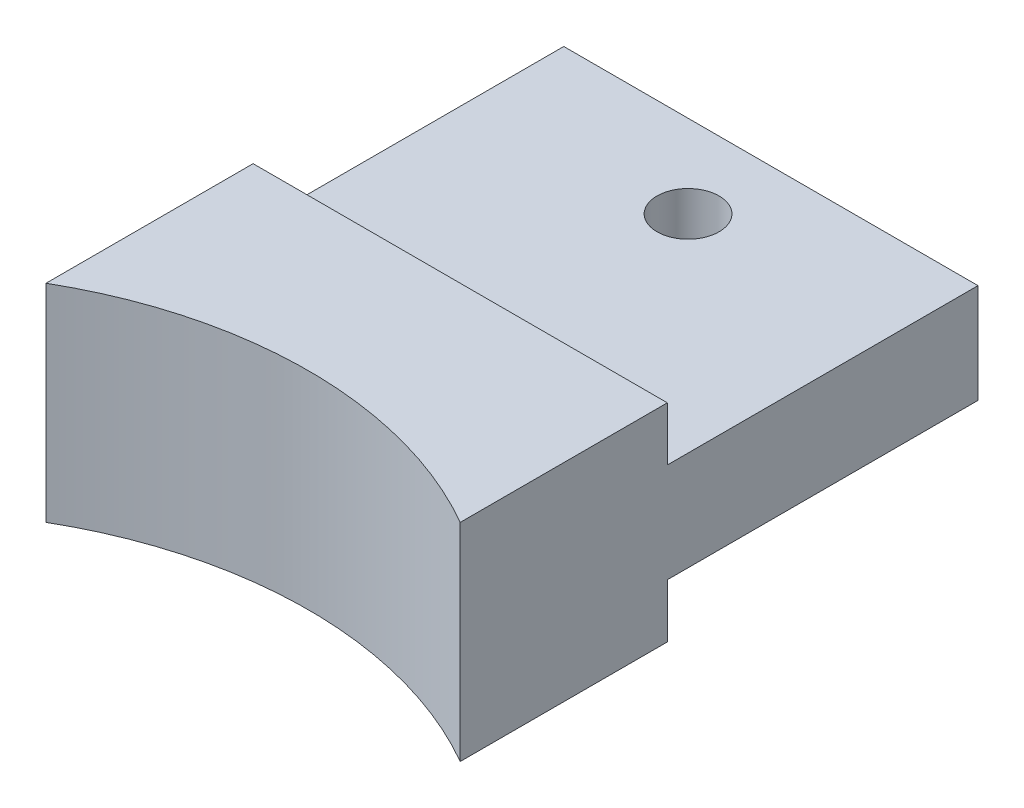
SolidWorks part; units mm, degrees
ref_plane "Front Plane" through (0, 0, 0) normal (0, 0, 1) x (1, 0, 0)
ref_plane "Top Plane" through (0, 0, 0) normal (0, 1, 0) x (1, 0, 0)
ref_plane "Right Plane" through (0, 0, 0) normal (1, 0, 0) x (0, 0, -1)
sketch "Sketch1" plane through (0, 0, 0) normal (0, 0, 1) x (1, 0, 0)
  line L1 (-10, -5) -> (10, -5)
  line L2 (-10, -5) -> (-10, 5)
  line L3 (-10, 5) -> (10, 5)
  line L4 (10, -5) -> (10, 5)
  line L5 (-10, -5) -> (10, 5) construction
  line L6 (-10, 5) -> (10, -5) construction
  point P0 (0, 0)
  dimension "D1" = 10
  dimension "D2" = 20
extrude "Boss-Extrude1" add sketch "Sketch1" along normal blind 10
sketch "Sketch2" plane through (0, 5, 0) normal (0, 1, 0) x (1, 0, 0)
  line L0 (-10, -10) -> (10, -10)
  arc A0 (-10, -10) -> (10, -10) centre (0, -27.3205) cw
  dimension "D1" = 20
extrude "Cut-Extrude1" cut sketch "Sketch2" against normal up to surface (10 mm away) up to face at (0, -5, 5)
sketch "Sketch3" plane through (0, 0, 0) normal (0, 0, -1) x (-1, 0, 0)
  line L0 (10, 5) -> (10, -5) construction
  line L1 (-10, -2.4) -> (10, -2.4)
  line L2 (-10, -2.4) -> (-10, 2.4)
  line L3 (-10, 2.4) -> (10, 2.4)
  line L4 (10, -2.4) -> (10, 2.4)
  line L5 (-10, -2.4) -> (10, 2.4) construction
  line L6 (-10, 2.4) -> (10, -2.4) construction
  point P0 (0, 0)
  dimension "D1" = 4.8
extrude "Boss-Extrude2" add sketch "Sketch3" along normal blind 15 contours L3 L4 L1 L2
hole_wizard "Tap Drill for M3x0.5 Tap6" positions "Sketch18" profile "Sketch19" hole size "M3x0.5" standard "ANSI Metric" end condition up to next
sketch "Sketch18" plane through (0, 2.4, 0) normal (0, 1, 0) x (1, 0, 0)
  line L2 (10, 15) -> (-10, 15) construction
  point P0 (0, 11)
  point P18 (0, 0)
  point P19 (0, 0)
  point P20 (0, 0)
  point P21 (0, 0)
  point P22 (0, 0)
  dimension "D1" = 4
sketch "Sketch19" plane through (0, 2.4, -11) normal (1, 0, 0) x (0, 0, 1)
  line L0 (0, 0) -> (0, 4.8)
  line L1 (0, 4.8) -> (1.5, 4.8)
  line L2 (1.5, 4.8) -> (1.5, 0)
  line L5 (1.5, 0) -> (0, 0)
  line L11 (0, -6.35) -> (0, 107.95) construction
  dimension "Thru Hole Dia." = 3
  dimension "Thru Hole Depth" = 4.8
